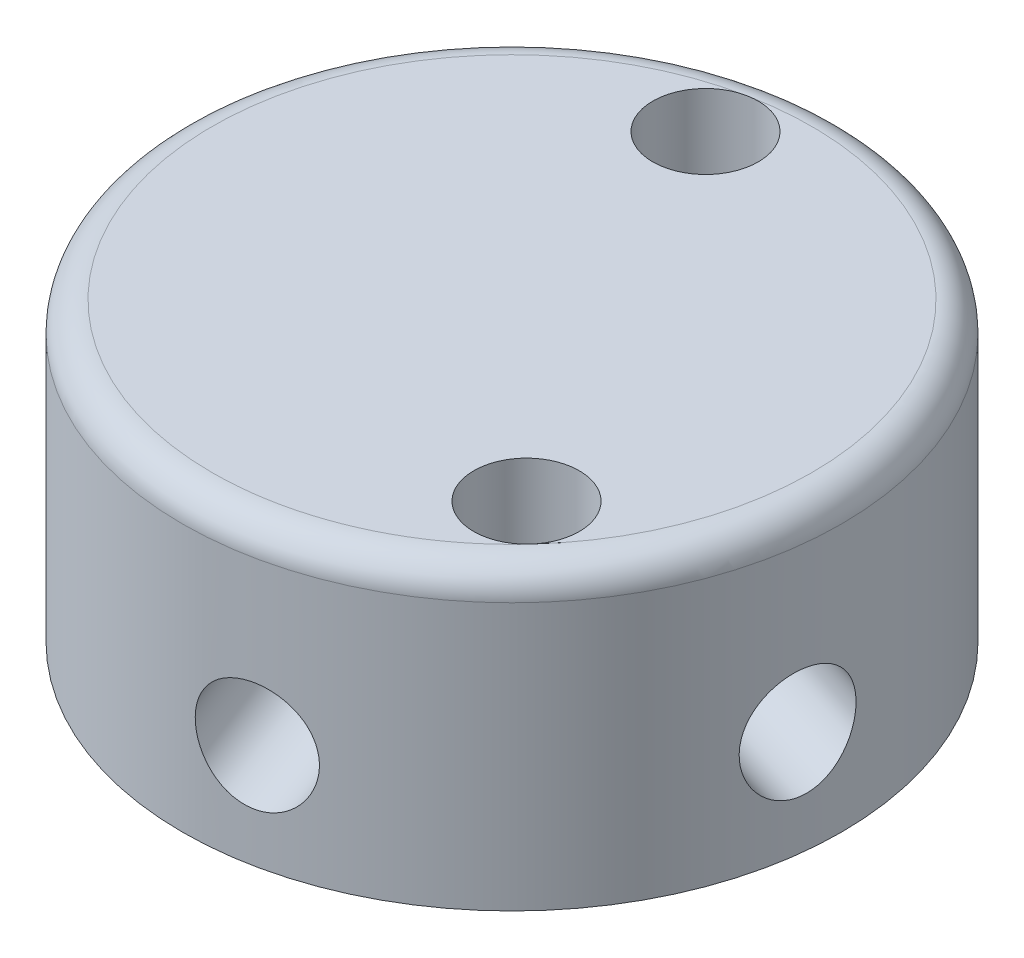
SolidWorks part; units mm, degrees
ref_plane "Front Plane" through (0, 0, 0) normal (0, 0, 1) x (1, 0, 0)
ref_plane "Top Plane" through (0, 0, 0) normal (0, 1, 0) x (1, 0, 0)
ref_plane "Right Plane" through (0, 0, 0) normal (1, 0, 0) x (0, 0, -1)
sketch "Sketch1" plane through (0, 0, 0) normal (0, 1, 0) x (1, 0, 0)
  circle A0 centre (0, 0) radius 10
  dimension "D1" = 20
extrude "Boss-Extrude1" add sketch "Sketch1" along normal blind 3 and the other way blind 6
ref_axis "5hubaxis" through (0, 5.5, 0) along (0, -1, 0)
ref_plane "holeplane" through (-3.3529, -1.0931, 1.8877) normal (0.8382, 0.2733, -0.4719) x (-0.4487, -0.1463, -0.8816)
sketch "Sketch4" plane through (-3.3529, -1.0931, 1.8877) normal (0.8382, 0.2733, -0.4719) x (-0.4487, -0.1463, -0.8816)
  circle A0 centre (0, 0) radius 1.5 construction
  circle A1 centre (0, 0) radius 1.5 construction
  circle A2 centre (0, 0) radius 1.6
  dimension "D1" = 3.2
extrude "hole" cut sketch "Sketch4" against normal through all
pattern_circular "holecir" count 5 over 360 about axis through (0, 5.5, 0) along (0, -1, 0) of "hole"
fillet "Fillet3" radius 0.9 1 edges at (0, 3, 10)
sketch "Sketch5" plane through (0, -6, 0) normal (0, -1, 0) x (1, 0, 0)
  circle A0 centre (0, 0) radius 3.5
  dimension "D1" = 7
extrude "Cut-Extrude1" cut sketch "Sketch5" against normal blind 2.6
sketch "Sketch6" plane through (0, 3, 0) normal (0, 1, 0) x (1, 0, 0)
  line L0 (0, 0) -> (-7.3586, 6.7713) construction
  line L1 (-1.748, 3.7828) -> (-6.1804, 7.8615) construction
  line L2 (0, 0) -> (4.166, 9.0909) construction
  line L3 (2.6578, 9.6404) -> (0.1484, 4.1645) construction
  line L4 (0, 0) -> (-1.9732, 9.8034) construction
  line L5 (0, 0) -> (9.9333, -1.1528) construction
  line L6 (3.6376, -2.0329) -> (9.6209, -2.7273) construction
  line L7 (0, 0) -> (7.3586, -6.7713) construction
  circle A0 centre (-1.4799, 7.3525) radius 1.6
  circle A1 centre (5.519, -5.0785) radius 1.6
  circle A2 centre (0, 0) radius 7.5 construction
  circle A3 centre (0, 0) radius 10 construction
  dimension "D1" = 3.2
  dimension "D2" = 15
  dimension "D5" = 3.2
  dimension "D3" = 36
  dimension "D4" = 36
extrude "Cut-Extrude2" cut sketch "Sketch6" against normal through all
